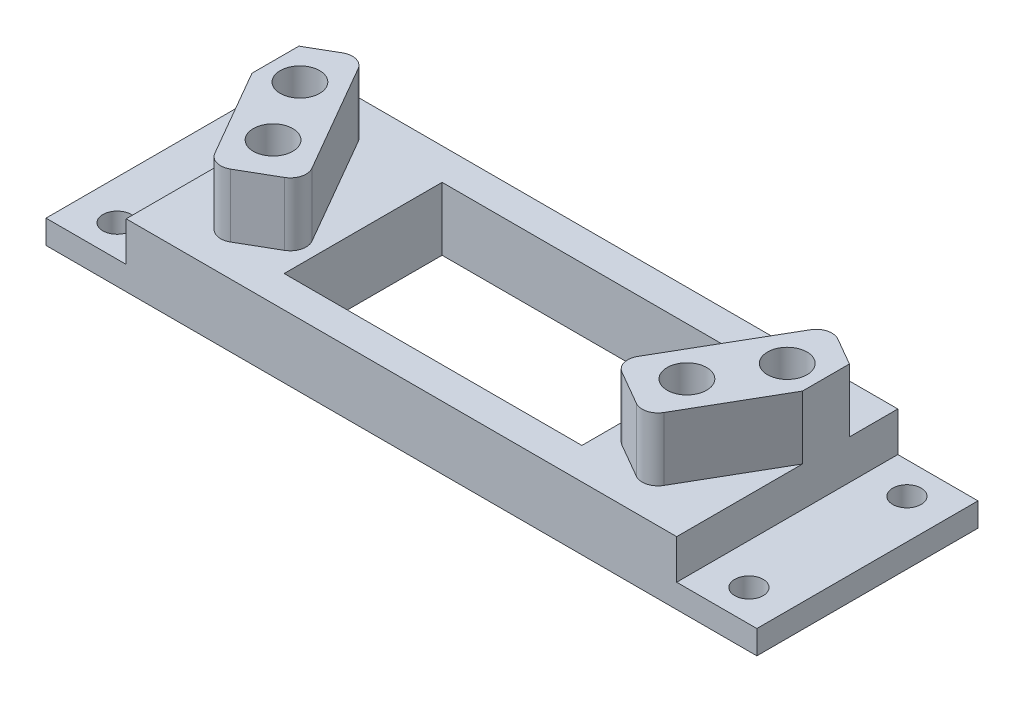
SolidWorks part; units mm, degrees
note: The reader was unsure of these and kept them because the rebuilt part matched: shared geometry of "Sketch1<3>".
ref_plane "Front Plane" through (0, 0, 0) normal (0, 0, 1) x (1, 0, 0)
ref_plane "Top Plane" through (0, 0, 0) normal (0, 1, 0) x (1, 0, 0)
ref_plane "Right Plane" through (0, 0, 0) normal (1, 0, 0) x (0, 0, -1)
sketch "Sketch1" plane through (0, 0, 0) normal (0, 1, 0) x (1, 0, 0)
  line L1 (34.85, -14) -> (-34.85, -14)
  line L2 (34.85, -14) -> (34.85, 14)
  line L3 (34.85, 14) -> (-34.85, 14)
  line L4 (-34.85, -14) -> (-34.85, 14)
  line L5 (34.85, -14) -> (-34.85, 14) construction
  line L6 (34.85, 14) -> (-34.85, -14) construction
  line L7 (45, -14) -> (-45, -14)
  line L8 (45, -14) -> (45, 14)
  line L9 (45, 14) -> (-45, 14)
  line L10 (-45, -14) -> (-45, 14)
  line L11 (45, -14) -> (-45, 14) construction
  line L12 (45, 14) -> (-45, -14) construction
  point P0 (0, 0)
  point P6 (0, 0)
  dimension "D1" = 69.7
  dimension "D2" = 90
  dimension "D3" = 28
extrude "Boss-Extrude1" add sketch "Sketch1" along normal blind 3 contours L10 L7 L4 L9 | L4 L1 L2 L3 | L8 L9 L2 L7
extrude "Boss-Extrude2" add sketch "Sketch1<3>" along normal blind 8 contours L4 L1 L2 L3
sketch "Sketch1<3>" plane through (0, 0, 0) normal (0, 1, 0) x (1, 0, 0) same geometry as "Sketch1"
sketch "Sketch2" plane through (0, 8, 0) normal (0, -1, 0) x (1, 0, 0)
  line L0 (-26.2, 4.054) -> (-30.85, -4) construction
  line L4 (-34.85, 14) -> (-34.85, -14)
  line L5 (34.85, 14) -> (-34.85, 14)
  line L6 (34.85, -14) -> (34.85, 14)
  line L7 (-34.85, -14) -> (34.85, -14)
  line L8 (-34.85, 14) -> (-34.85, -14)
  line L9 (34.85, 14) -> (-34.85, 14)
  line L10 (34.85, -14) -> (34.85, 14)
  line L11 (-34.85, -14) -> (34.85, -14)
  circle A0 centre (-30.85, -4) radius 2.5
  circle A1 centre (-26.2, 4.054) radius 2.5
  dimension "D4" = 5
  dimension "D2" = 9.3
  dimension "D3" = 30
  dimension "D5" = 10
  dimension "D6" = 4
  dimension "D1" = 0
extrude "Cut-Extrude1" cut sketch "Sketch2" along normal blind 6
sketch "Sketch3" plane through (0, 8, 0) normal (0, -1, 0) x (1, 0, 0)
  line L0 (-19.6279, 6.4373) -> (-29.6279, -10.8832)
  line L1 (-19.6279, 6.4373) -> (-27.4221, 10.9373)
  line L2 (-29.6279, -10.8832) -> (-37.4221, -6.3832)
  line L3 (-27.4221, 10.9373) -> (-37.4221, -6.3832)
  line L4 (-19.6279, 6.4373) -> (-37.4221, -6.3832) construction
  line L5 (-29.6279, -10.8832) -> (-27.4221, 10.9373) construction
  line L6 (-45, 14) -> (-45, -14) construction
  line L7 (-26.2, 4.054) -> (-30.85, -4) construction
  line L12 (-34.85, 14) -> (-34.85, -14)
  line L13 (34.85, 14) -> (-34.85, 14)
  line L14 (34.85, -14) -> (34.85, 14)
  line L15 (-34.85, -14) -> (34.85, -14)
  line L16 (-34.85, 14) -> (-34.85, -14)
  line L17 (34.85, 14) -> (-34.85, 14)
  line L18 (34.85, -14) -> (34.85, 14)
  line L19 (-34.85, -14) -> (34.85, -14)
  circle A0 centre (-26.2, 4.054) radius 2.5 construction
  circle A1 centre (-30.85, -4) radius 2.5 construction
  circle A2 centre (-26.2, 4.054) radius 2.5
  circle A3 centre (-30.85, -4) radius 2.5
  point P1 (-28.525, 0.027)
  point P14 (-28.525, 0.027)
  line M13 (-34.85, -14) -> (-34.85, 14)
  circle M17 centre (-30.85, -4) radius 2.5
  circle M18 centre (-26.2, 4.054) radius 2.5
  dimension "D1" = 30
  dimension "D2" = 9
  dimension "D3" = 20
  dimension "D4" = 0
extrude "Boss-Extrude3" add sketch "Sketch3" against normal blind 8 contours L3 L1 L0 L2 M13 M18 M17
fillet "Fillet1" radius 2 3 edges at (-29.6279, 12, -10.8832) (-19.6279, 12, 6.4373) (-27.4221, 12, 10.9373)
mirror "Mirror1" about plane through (0, 0, 0) normal (1, 0, 0) of "Cut-Extrude1", "Fillet1", "Boss-Extrude3"
sketch "Sketch4" plane through (0, 3, 0) normal (0, 1, 0) x (1, 0, 0)
  line L0 (-45, -14) -> (-45, 14) construction
  line L1 (45, -14) -> (45, 14) construction
  line L2 (45, 14) -> (34.85, 14) construction
  line L3 (-34.85, 14) -> (-45, 14) construction
  line L4 (-34.85, -14) -> (-45, -14) construction
  line L5 (45, -14) -> (34.85, -14) construction
  point P0 (-40, 10)
  point P2 (-40, -10)
  point P4 (40, -10)
  point P6 (40, 10)
  dimension "D1" = 5
  dimension "D2" = 5
  dimension "D3" = 4
  dimension "D4" = 4
  dimension "D5" = 4
  dimension "D6" = 4
hole_wizard "M3 Clearance Hole1" positions "Sketch4" profile "Sketch5" hole size "M3" standard "ANSI Metric"
sketch "Sketch5" plane through (-40, 3, -10) normal (1, 0, 0) x (0, 0, 1)
  line L0 (0, 0) -> (0, 11.0815)
  line L1 (0, 11.0815) -> (1.8, 10)
  line L2 (1.8, 10) -> (1.8, 0)
  line L5 (1.8, 0) -> (0, 0)
  line L10 (0, 11.0815) -> (-1.8, 10) construction
  line L11 (0, -6.35) -> (0, 107.95) construction
  dimension "Hole Dia." = 3.6
  dimension "Hole Depth" = 10
  dimension "Drill Angle" = 118
sketch "Sketch6" plane through (0, 8, 0) normal (0, 1, 0) x (1, 0, 0)
  line L0 (34.85, 14) -> (-34.85, 14) construction
  line L1 (-18.85, -10) -> (18.85, -10)
  line L2 (-18.85, -10) -> (-18.85, 10)
  line L3 (-18.85, 10) -> (18.85, 10)
  line L4 (18.85, -10) -> (18.85, 10)
  line L5 (-18.85, -10) -> (18.85, 10) construction
  line L6 (-18.85, 10) -> (18.85, -10) construction
  line L7 (-34.85, 7.8682) -> (-34.85, 14) construction
  line L8 (34.85, -14) -> (34.85, 1.9282) construction
  point P0 (0, 0)
  dimension "D1" = 4
  dimension "D2" = 16
  dimension "D3" = 16
  dimension "D4" = 20
extrude "Cut-Extrude2" cut sketch "Sketch6" against normal through all contours L1 L4 L3 L2
